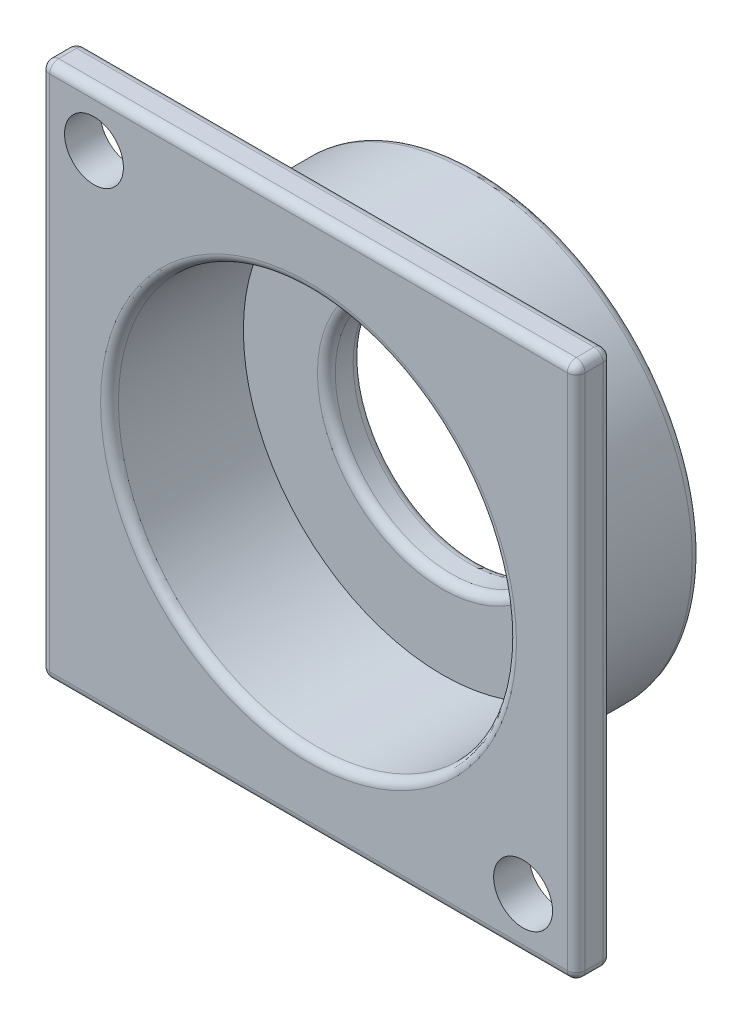
SolidWorks part; units mm, degrees
ref_plane "Front Plane" through (0, 0, 0) normal (0, 0, 1) x (1, 0, 0)
ref_plane "Top Plane" through (0, 0, 0) normal (0, 1, 0) x (1, 0, 0)
ref_plane "Right Plane" through (0, 0, 0) normal (1, 0, 0) x (0, 0, -1)
sketch "Sketch1" plane through (0, 0, 0) normal (0, 0, 1) x (1, 0, 0)
  line L0 (0, 0) -> (-12.0208, 12.0208)
  line L1 (15, -15) -> (-15, -15)
  line L2 (15, -15) -> (15, 15)
  line L3 (15, 15) -> (-15, 15)
  line L4 (-15, -15) -> (-15, 15)
  line L5 (0, 15) -> (0, -15) construction
  line L6 (15, 0) -> (-15, 0) construction
  line L7 (0, 0) -> (12.0208, -12.0208)
  circle A0 centre (0, 0) radius 11 construction
  circle A2 centre (-12.0208, 12.0208) radius 1.65
  circle A3 centre (12.0208, -12.0208) radius 1.65
  circle A4 centre (0, 0) radius 12.5
  circle A5 centre (0, 0) radius 11.15
  dimension "D2" = 22
  dimension "D4" = 3.3
  dimension "D7" = 25
  dimension "D1" = 30
  dimension "D5" = 17
  dimension "D6" = 45
  dimension "D9" = 30
  dimension "D8" = 0.15
extrude "Boss-Extrude1" add sketch "Sketch1" against normal blind 2 contours A5 L7 A4 L0 | A5 L0 A4 L7 | L4 L1 L2 L3 A4 A2 A3 region at (-8.0976, -8.0976, 0) region at (-8.1481, 8.5749, 0) region at (0, -14.5757, 0)
extrude "Boss-Extrude2" add sketch "Sketch1<3>" against normal blind 7.5 contours A5 L0 A4 L7 | A5 L7 A4 L0 region at (-8.0976, -8.0976, 0) region at (-8.1481, 8.5749, 0)
sketch "Sketch1<3>" plane through (0, 0, 0) normal (0, 0, 1) x (1, 0, 0) same geometry as "Sketch1"
sketch "Sketch2" plane through (0, 0, -7.5) normal (0, 0, -1) x (-1, 0, 0)
  circle A0 centre (0, 0) radius 12.5
  circle A1 centre (0, 0) radius 6.5
  dimension "D1" = 25
  dimension "D2" = 13
extrude "Boss-Extrude3" add sketch "Sketch2" along normal blind 2
fillet "Fillet1" radius 0.5 16 edges at (0, -15, -2) (0, -15, 0) (-15, -15, -1) (-15, 0, -2) (-15, 0, 0) (-15, 15, -1) (0, 15, -2) (0, 15, 0) (15, 15, -1) (15, 0, -2) (15, -15, -1) (15, 0, 0) (11.15, 0, 0) (-12.5, 0, -9.5) (-6.5, 0, -7.5) (-6.5, 0, -9.5)
